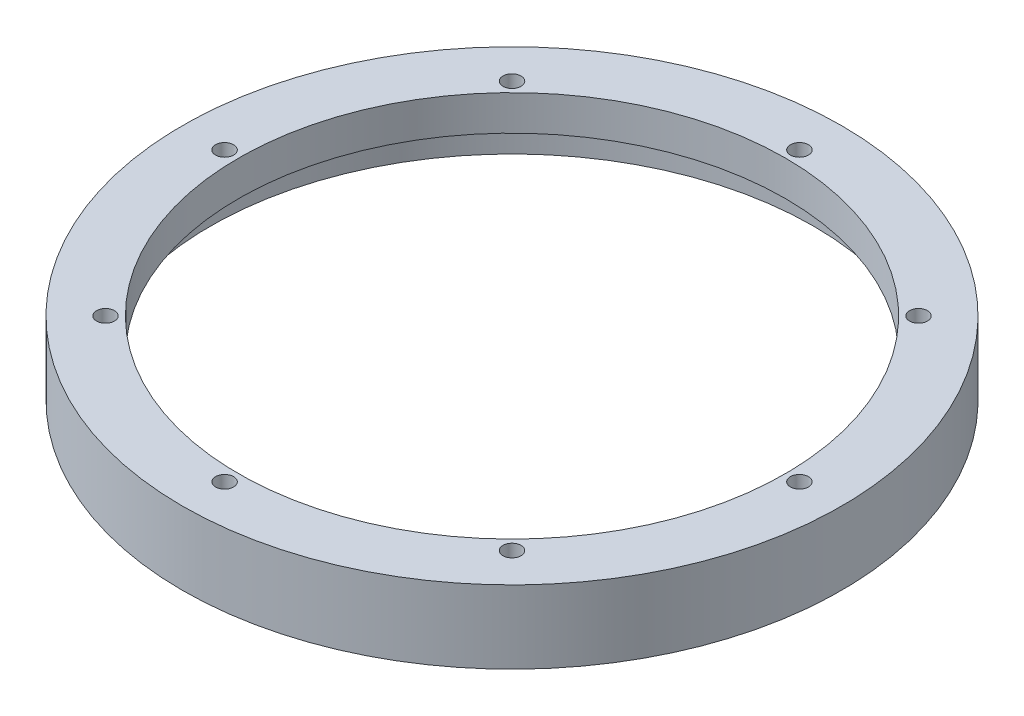
SolidWorks part; units mm, degrees
material "6061-T6 (SS)"
ref_plane "Front Plane" through (0, 0, 0) normal (0, 0, 1) x (1, 0, 0)
ref_plane "Top Plane" through (0, 0, 0) normal (0, 1, 0) x (1, 0, 0)
ref_plane "Right Plane" through (0, 0, 0) normal (1, 0, 0) x (0, 0, -1)
sketch "Sketch1" plane through (0, 0, 0) normal (0, 0, 1) x (1, 0, 0)
  line L0 (-49.4665, 0) -> (-59.6265, 0)
  line L1 (-59.6265, 0) -> (-59.6265, -13.208)
  line L2 (-59.6265, -13.208) -> (-54.5465, -13.208)
  line L3 (-54.5465, -13.208) -> (-54.5465, -6.35)
  line L4 (-54.5465, -6.35) -> (-49.4665, -6.35)
  line L5 (-49.4665, -6.35) -> (-49.4665, 0)
  line L6 (0, 0) -> (0, 8.0765) construction
  dimension "D1" = 49.4665
  dimension "D2" = 54.5465
  dimension "D3" = 5.08
  dimension "D4" = 13.208
  dimension "D5" = 6.35
revolve "Revolve1" add sketch "Sketch1" angle 360 about L6
sketch "Sketch2" plane through (0, 0, 0) normal (0, 1, 0) x (1, 0, 0)
  line L0 (0, 49.4665) -> (0, 52.0065) construction
  circle A0 centre (0, 0) radius 49.4665 construction
  dimension "D1" = 2.54
hole_wizard "#4 Clearance Hole1" positions "3DSketch1" profile "Sketch3" hole size "#4" standard "Ansi Inch"
sketch3d "3DSketch1"
  point P0 (0, 0, -52.0065)
sketch "Sketch3" plane through (0, 0, -52.0065) normal (1, 0, 0) x (0, 0, 1)
  line L0 (0, 0) -> (0, 11.1406)
  line L1 (0, 11.1406) -> (1.6319, 10.16)
  line L2 (1.6319, 10.16) -> (1.6319, 0)
  line L5 (1.6319, 0) -> (0, 0)
  line L10 (0, 11.1406) -> (-1.632, 10.16) construction
  line L11 (0, -6.35) -> (0, 107.95) construction
  dimension "Hole Dia." = 3.2639
  dimension "Hole Depth" = 10.16
  dimension "Drill Angle" = 118
pattern_circular "CirPattern1" count 8 over 360 about axis through (0, 0, 0) along (0, -1, 0) of "#4 Clearance Hole1"
